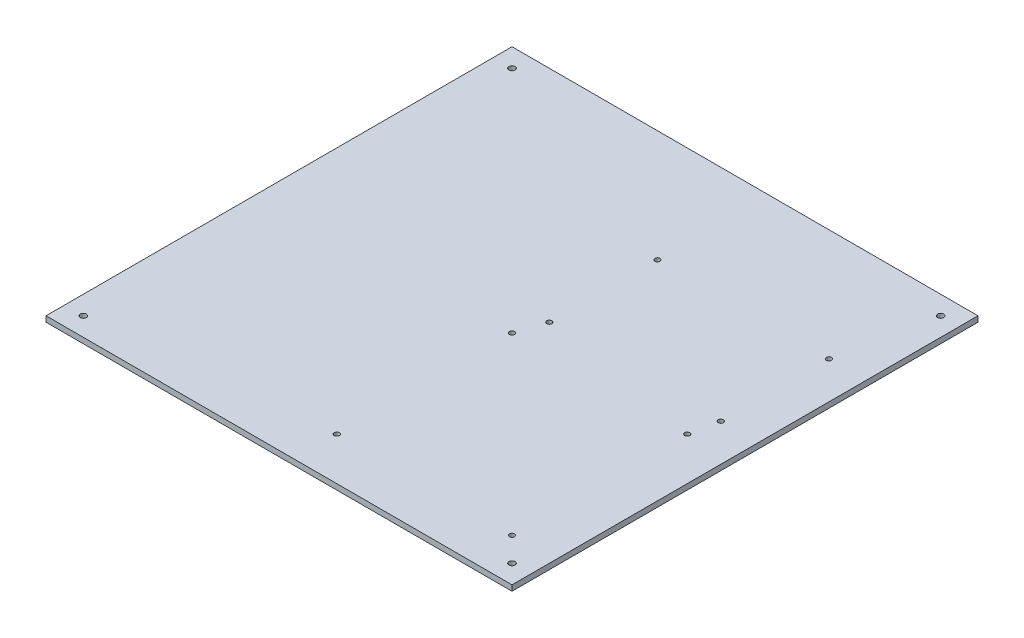
SolidWorks part; units mm, degrees
ref_plane "Front Plane" through (0, 0, 0) normal (0, 0, 1) x (1, 0, 0)
ref_plane "Top Plane" through (0, 0, 0) normal (0, 1, 0) x (1, 0, 0)
ref_plane "Right Plane" through (0, 0, 0) normal (1, 0, 0) x (0, 0, -1)
sketch "Sketch1" plane through (0, 0, 0) normal (0, 1, 0) x (1, 0, 0)
  line L0 (0, 0) -> (0, -250) construction
  line L1 (-125, 0) -> (125, 0)
  line L2 (-125, 0) -> (-125, -250)
  line L3 (-125, -250) -> (125, -250)
  line L4 (125, 0) -> (125, -250)
  line L5 (0, -1.65) -> (0, 1.65) construction
  line L6 (-125, -125) -> (125, -125) construction
  line L7 (55, -130) -> (55, -230) construction
  line L8 (-105, -161.34) -> (-31.34, -161.34) construction
  line L9 (-105, -15) -> (-31.34, -15) construction
  line L10 (-105, -15) -> (-105, -88.66) construction
  line L11 (-105, -88.66) -> (-31.34, -88.66) construction
  line L12 (-31.34, -15) -> (-31.34, -88.66) construction
  line L13 (-105, -161.34) -> (-105, -235) construction
  line L14 (-105, -235) -> (-31.34, -235) construction
  line L15 (-31.34, -161.34) -> (-31.34, -235) construction
  line L16 (-105, -88.66) -> (-105, -161.34) construction
  line L17 (5, -130) -> (105, -130) construction
  line L18 (5, -130) -> (5, -230) construction
  line L19 (5, -230) -> (105, -230) construction
  line L20 (105, -130) -> (105, -230) construction
  line L21 (5, -180) -> (105, -180) construction
  line L22 (-60.805, -122.8687) -> (-38.005, -122.8687) construction
  line L23 (9, -43) -> (109, -43) construction
  line L24 (9, -43) -> (9, -122) construction
  line L25 (9, -122) -> (109, -122) construction
  line L26 (109, -43) -> (109, -122) construction
  line L27 (-102.037, -122.1462) -> (-79.237, -122.1462) construction
  line L28 (-102.037, -122.1462) -> (-102.037, -145.0462) construction
  line L29 (-102.037, -145.0462) -> (-79.237, -145.0462) construction
  line L30 (-79.237, -122.1462) -> (-79.237, -145.0462) construction
  line L35 (-60.805, -122.8687) -> (-60.805, -145.7687) construction
  line L36 (-60.805, -145.7687) -> (-38.005, -145.7687) construction
  line L37 (-38.005, -122.8687) -> (-38.005, -145.7687) construction
  circle A3 centre (-115, -240) radius 1.65
  circle A4 centre (115, -240) radius 1.65
  circle A5 centre (-115, -10) radius 1.65
  circle A6 centre (115, -10) radius 1.65
  circle A7 centre (13, -60) radius 1.375
  circle A8 centre (13, -118) radius 1.375
  circle A9 centre (105, -118) radius 1.375
  circle A10 centre (105, -60) radius 1.375
  circle A11 centre (8, -133) radius 1.375
  circle A12 centre (102, -133) radius 1.375
  circle A13 centre (102, -227) radius 1.375
  circle A14 centre (8, -227) radius 1.375
  dimension "D1" = 3.3
  dimension "D2" = 10
  dimension "D12" = 2.75
  dimension "D20" = 2.75
  dimension "D3" = 10
  dimension "D4" = 250
  dimension "D5" = 250
  dimension "D6" = 73.66
  dimension "D7" = 15
  dimension "D8" = 20
  dimension "D9" = 58
  dimension "D10" = 92
  dimension "D11" = 58
  dimension "D13" = 20
  dimension "D14" = 60
  dimension "D15" = 100
  dimension "D16" = 100
  dimension "D17" = 20
  dimension "D18" = 20
  dimension "D19" = 3
  dimension "D21" = 3
  dimension "D22" = 17
  dimension "D23" = 79
  dimension "D24" = 100
  dimension "D25" = 4
  dimension "D26" = 22.9
  dimension "D27" = 22.8
extrude "Boss-Extrude1" add sketch "Sketch1" along normal blind 3
equation "\"cf_tube_outer_diameter\" = 25mm"
equation "\"cf_tube_inner_diameter\" = 21mm"
equation "\"mid_plate_mid_to_top\" = 100mm"
equation "\"mid_plate_mid_to_bottom\" = 30mm"
equation "\"mid_plate_horizontal_spacing\" = 250mm"
equation "\"cf_plate_thickness\" = 4mm"
equation "\"mid_tube_length\" = 500mm"
equation "\"mid_plate_bottom_width\"= 180mm"
equation "\"mid_support_plate_distance\" = 250mm"
equation "\"nut_strip_2_hole_distance\" = 7mm"
equation "\"nut_strip_hole_diameter\" = 2.5mm"
equation "\"nut_strip_hole_to_edge_distance\" = 2.5mm"
